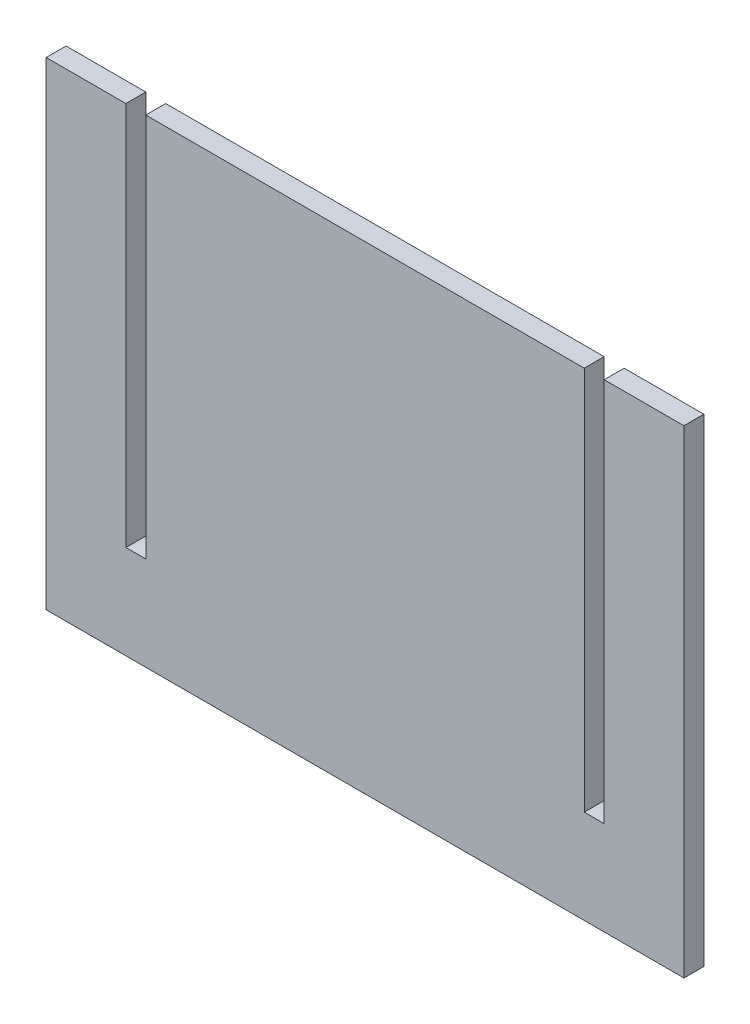
SolidWorks part; units mm, degrees
ref_plane "Front Plane" through (0, 0, 0) normal (0, 0, 1) x (1, 0, 0)
ref_plane "Top Plane" through (0, 0, 0) normal (0, 1, 0) x (1, 0, 0)
ref_plane "Right Plane" through (0, 0, 0) normal (1, 0, 0) x (0, 0, -1)
sketch "Sketch1" plane through (0, 0, 0) normal (0, 0, 1) x (1, 0, 0)
  line L0 (50.8, 76.2) -> (50.8, 0) construction
  line L1 (0, 0) -> (101.6, 0)
  line L2 (0, 0) -> (0, 76.2)
  line L3 (0, 76.2) -> (101.6, 76.2)
  line L4 (101.6, 0) -> (101.6, 76.2)
  line L5 (12.7, 76.2) -> (15.875, 76.2)
  line L6 (12.7, 76.2) -> (12.7, 14.9428)
  line L7 (12.7, 14.9428) -> (15.875, 14.9428)
  line L8 (15.875, 76.2) -> (15.875, 14.9428)
  line L9 (88.9, 14.9428) -> (85.725, 14.9428)
  line L10 (85.725, 76.2) -> (85.725, 14.9428)
  line L11 (88.9, 76.2) -> (88.9, 14.9428)
  dimension "D1" = 101.6
  dimension "D2" = 76.2
  dimension "D3" = 12.7
  dimension "D4" = 3.175
extrude "Boss-Extrude1" add sketch "Sketch1" along normal blind 3.175 contours L0 L3 L8 L7 L6 L2 L1 | L3 L0 L1 L4 L11 L9 L10 region at (75.6121, 37.7047, 0) region at (25.9879, 37.7047, 0)
